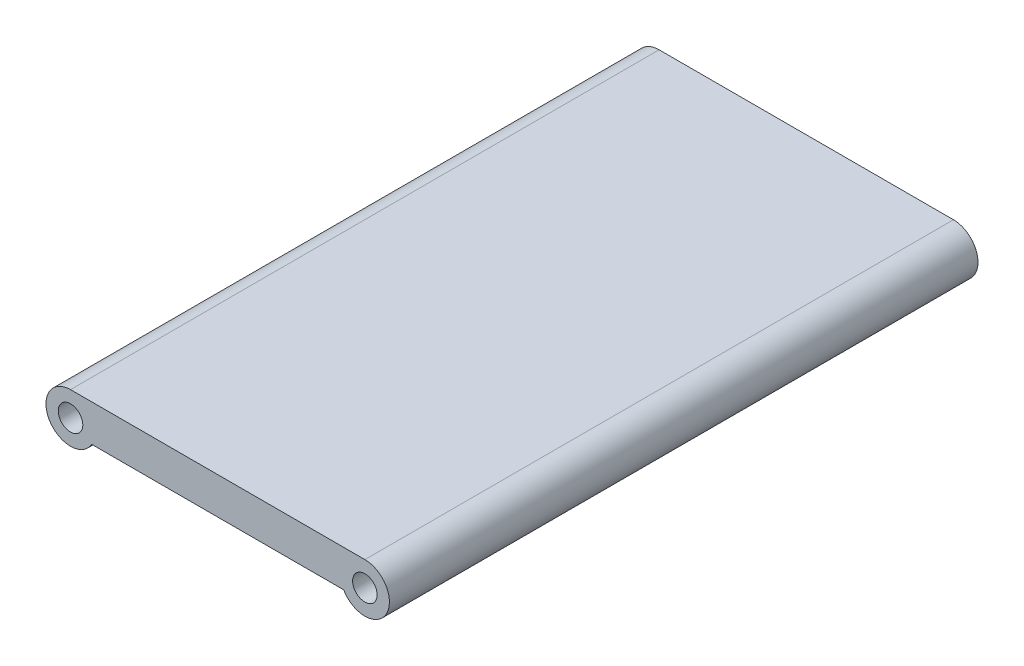
SolidWorks part; units mm, degrees
ref_plane "Front Plane" through (0, 0, 0) normal (0, 0, 1) x (1, 0, 0)
ref_plane "Top Plane" through (0, 0, 0) normal (0, 1, 0) x (1, 0, 0)
ref_plane "Right Plane" through (0, 0, 0) normal (1, 0, 0) x (0, 0, -1)
sketch "Sketch2" plane through (0, 0, 0) normal (0, 0, 1) x (1, 0, 0)
  line L0 (-38.1088, 6.35) -> (38.1088, 6.35)
  line L1 (-32.6095, -3.175) -> (32.6095, -3.175)
  arc A0 (-32.6095, -3.175) -> (-38.1088, 6.35) centre (-38.1088, 0) cw
  arc A1 (32.6095, -3.175) -> (38.1088, 6.35) centre (38.1088, 0) ccw
  point P16 (0, 6.35)
  dimension "D3" = 6.35
  dimension "D2" = 76.2175
  dimension "D4" = 9.525
extrude "Boss-Extrude1" add sketch "Sketch2" along normal blind 152.4 contours L0 A1 L1 A0
sketch "Sketch3" plane through (0, 0, 0) normal (0, 0, -1) x (-1, 0, 0)
  circle A0 centre (-38.1088, 0) radius 3.175
  circle A1 centre (38.1088, 0) radius 3.175
  dimension "D1" = 6.35
extrude "Cut-Extrude1" cut sketch "Sketch3" against normal through all
